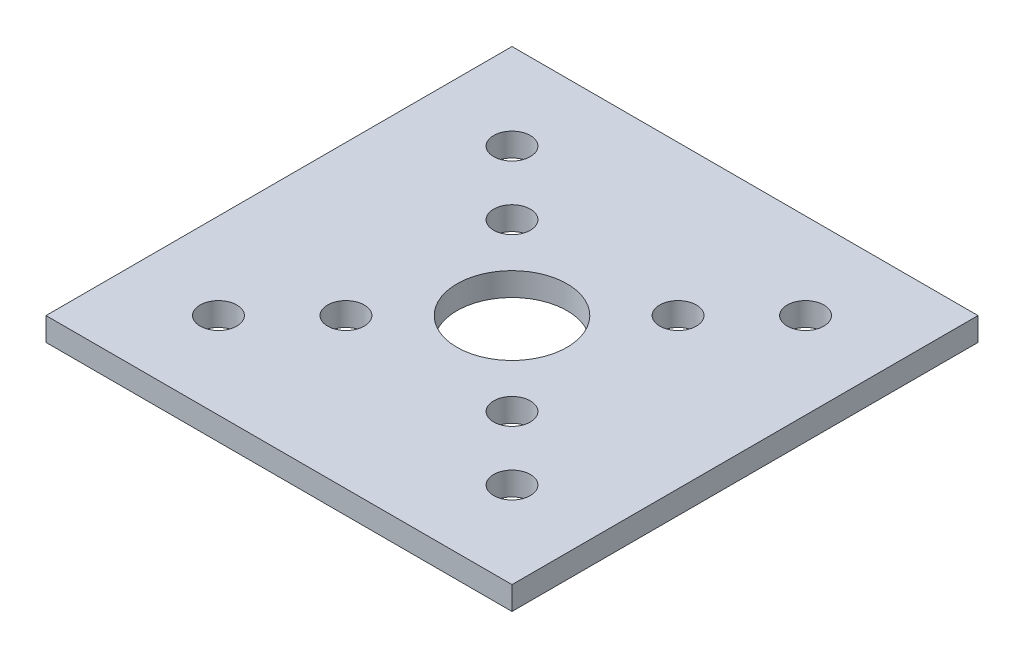
SolidWorks part; units mm, degrees
ref_plane "Front Plane" through (0, 0, 0) normal (0, 0, 1) x (1, 0, 0)
ref_plane "Top Plane" through (0, 0, 0) normal (0, 1, 0) x (1, 0, 0)
ref_plane "Right Plane" through (0, 0, 0) normal (1, 0, 0) x (0, 0, -1)
sketch "Sketch1" plane through (0, 0, 0) normal (0, 1, 0) x (1, 0, 0)
  line L1 (-31.75, -31.75) -> (31.75, -31.75)
  line L2 (-31.75, -31.75) -> (-31.75, 31.75)
  line L3 (-31.75, 31.75) -> (31.75, 31.75)
  line L4 (31.75, -31.75) -> (31.75, 31.75)
  line L5 (-31.75, -31.75) -> (31.75, 31.75) construction
  line L6 (-31.75, 31.75) -> (31.75, -31.75) construction
  point P0 (0, 0)
  dimension "D1" = 63.5
  dimension "D2" = 63.5
extrude "Boss-Extrude1" add sketch "Sketch1" along normal blind 3.175
sketch "Sketch2" plane through (0, 3.175, 0) normal (0, 1, 0) x (1, 0, 0)
  line L0 (0, 0) -> (11.3137, 11.3137) construction
  line L1 (0, 0) -> (0, 7.779) construction
  line L3 (-20, -20) -> (20, -20) construction
  line L4 (-20, -20) -> (-20, 20) construction
  line L5 (-20, 20) -> (20, 20) construction
  line L6 (20, -20) -> (20, 20) construction
  line L7 (-20, -20) -> (20, 20) construction
  line L8 (-20, 20) -> (20, -20) construction
  circle A0 centre (0, 0) radius 16 construction
  circle A1 centre (11.3137, 11.3137) radius 2.5
  circle A2 centre (11.3137, -11.3137) radius 2.5
  circle A3 centre (-11.3137, -11.3137) radius 2.5
  circle A4 centre (-11.3137, 11.3137) radius 2.5
  circle A5 centre (0, 0) radius 7.5
  circle A6 centre (-20, -20) radius 2.5
  circle A7 centre (20, -20) radius 2.5
  circle A8 centre (20, 20) radius 2.5
  circle A9 centre (-20, 20) radius 2.5
  point P15 (0, 0)
  dimension "D1" = 5
  dimension "D2" = 32
  dimension "D5" = 15
  dimension "D8" = 5
  dimension "D3" = 45
  dimension "D6" = 40
  dimension "D7" = 40
  dimension "D4" = 4
extrude "Cut-Extrude1" cut sketch "Sketch2" against normal through all
